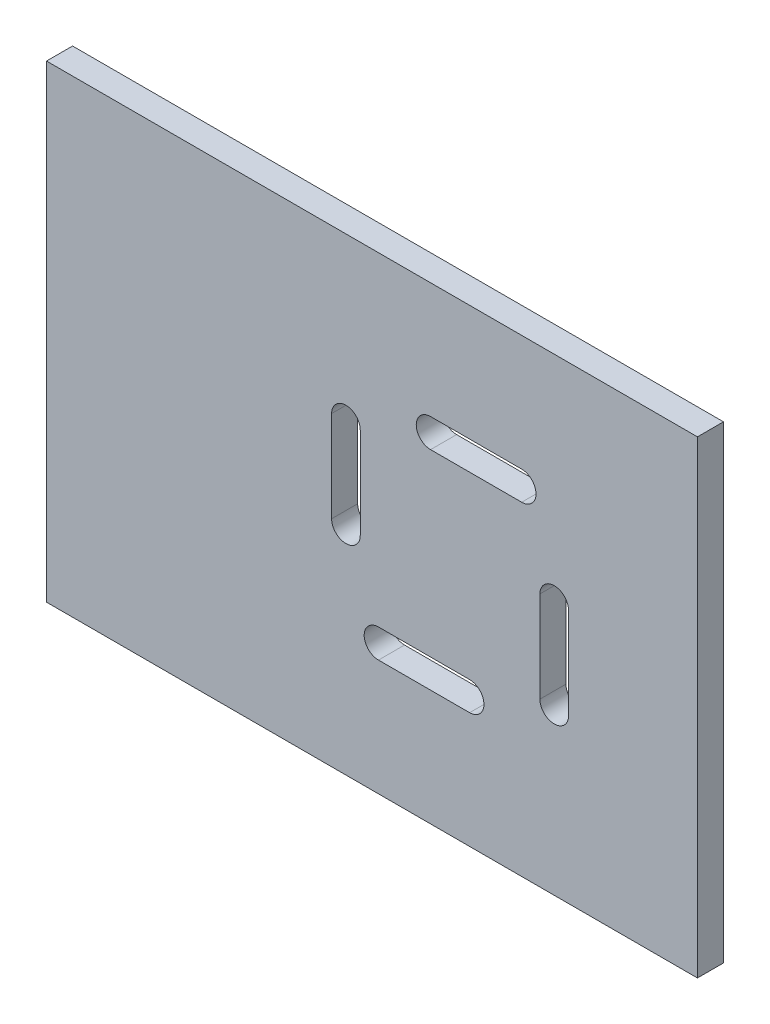
SolidWorks part; units mm, degrees
ref_plane "Front Plane" through (0, 0, 0) normal (0, 0, 1) x (1, 0, 0)
ref_plane "Top Plane" through (0, 0, 0) normal (0, 1, 0) x (1, 0, 0)
ref_plane "Right Plane" through (0, 0, 0) normal (1, 0, 0) x (0, 0, -1)
sketch "Sketch1" plane through (0, 0, 0) normal (0, 0, 1) x (1, 0, 0)
  line L1 (-50, 40) -> (200, 40)
  line L2 (-50, 40) -> (-50, -140)
  line L3 (-50, -140) -> (200, -140)
  line L4 (200, 40) -> (200, -140)
  point P4 (105, -50)
  dimension "D1" = 200
  dimension "D2" = 250
  dimension "D3" = 140
  dimension "D4" = 180
  dimension "D5" = 105
  dimension "D6" = 50
extrude "Boss-Extrude1" add sketch "Sketch1" along normal blind 10
ref_axis "Axis1" through (105, -50, 0) along (0, 0, 1)
sketch "Sketch2" plane through (0, 0, 10) normal (0, 0, 1) x (1, 0, 0)
  line L0 (65, -22.5) -> (65, -57.5) construction
  line L1 (70.5, -22.5) -> (70.5, -57.5)
  line L2 (59.5, -22.5) -> (59.5, -57.5)
  arc A0 (70.5, -22.5) -> (59.5, -22.5) centre (65, -22.5) ccw
  arc A1 (59.5, -57.5) -> (70.5, -57.5) centre (65, -57.5) ccw
  point P2 (65, -40)
  point P7 (0, 0)
  point P8 (65, -17)
  point P9 (65, -63)
  dimension "D1" = 10
  dimension "D4" = 46
  dimension "D2" = 40
  dimension "D3" = 11
extrude "Cut-Extrude1" cut sketch "Sketch2" against normal blind 10
pattern_circular "CirPattern1" count 4 over 360 about axis through (105, -50, 0) along (0, 0, 1) of "Cut-Extrude1"
